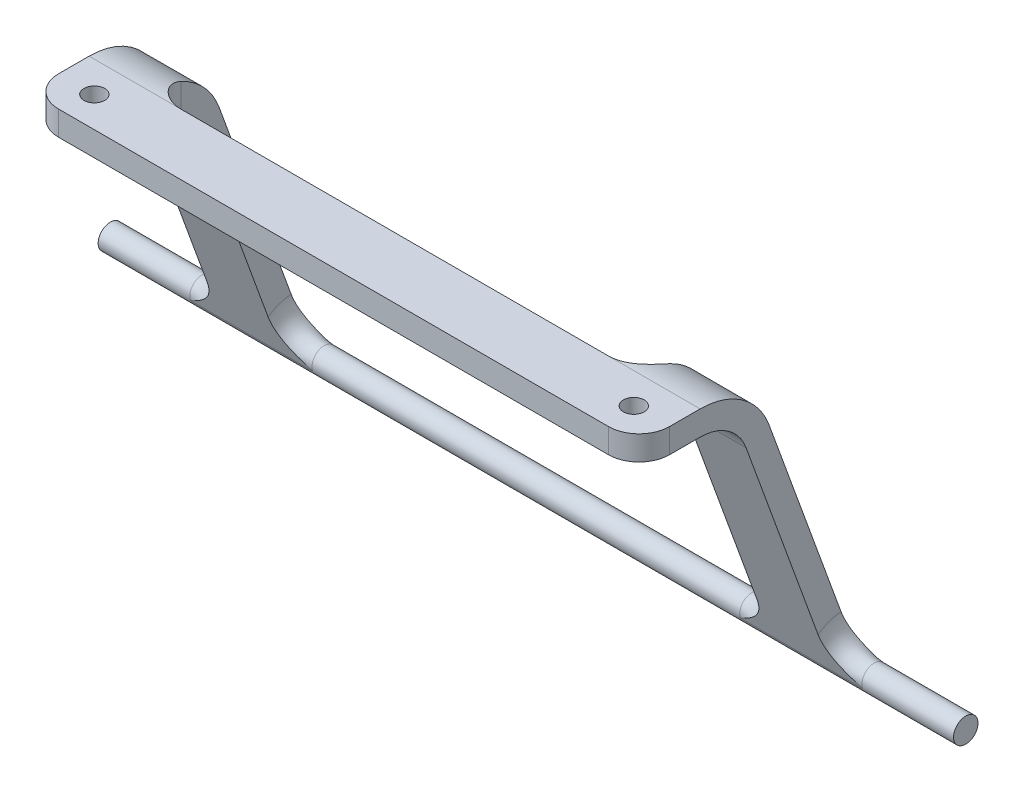
SolidWorks part; units mm, degrees
material "ABS PC"
ref_plane "Front Plane" through (0, 0, 0) normal (0, 0, 1) x (1, 0, 0)
ref_plane "Top Plane" through (0, 0, 0) normal (0, 1, 0) x (1, 0, 0)
ref_plane "Right Plane" through (0, 0, 0) normal (1, 0, 0) x (0, 0, -1)
sketch "Sketch1" plane through (0, 0, 0) normal (0, 1, 0) x (1, 0, 0)
  line L1 (-44.1422, -44.1422) -> (44.1422, -44.1422) construction
  line L2 (-44.1422, -44.1422) -> (-44.1422, 44.1422) construction
  line L3 (-44.1422, 44.1422) -> (44.1422, 44.1422) construction
  line L4 (44.1422, -44.1422) -> (44.1422, 44.1422) construction
  line L5 (-44.1422, -44.1422) -> (44.1422, 44.1422) construction
  line L6 (-44.1422, 44.1422) -> (44.1422, -44.1422) construction
  line L9 (-50, 39.1421) -> (50, 39.1421)
  line L10 (-50, 39.1421) -> (-50, 49.1421)
  line L11 (-50, 49.1421) -> (50, 49.1421)
  line L12 (50, 39.1421) -> (50, 49.1421)
  line L13 (-50, 39.1421) -> (50, 49.1421) construction
  line L14 (-50, 49.1421) -> (50, 39.1421) construction
  circle A0 centre (-44.1422, 44.1422) radius 1.7
  circle A1 centre (44.1422, 44.1422) radius 1.7
  point P0 (0, 0)
  point P8 (0, 44.1422)
  dimension "D2" = 3.4
  dimension "D3" = 3.4
  dimension "D4" = 10
  dimension "D1" = 88.2843
  dimension "D5" = 100
extrude "Boss-Extrude1" add sketch "Sketch1" along normal blind 4
sketch "Sketch3" plane through (50, 0, 0) normal (1, 0, 0) x (0, 0, -1)
  line L0 (49.1421, 4) -> (49.1421, 0) construction
  line L1 (49.1421, -8) -> (49.1421, 0) construction
  line L2 (49.1421, -8) -> (66.0085, -1.8612) construction
  line L3 (56.6597, -5.2638) -> (70.7395, -43.9479)
  line L4 (60.4185, -3.8958) -> (74.4983, -42.5798)
  line L5 (71.2185, -45.2638) -> (74.411, -45.2638) construction
  line L6 (49.1421, 4) -> (49.1421, 0)
  arc A0 (49.1421, 0) -> (56.6597, -5.2638) centre (49.1421, -8) cw
  arc A1 (49.1421, 4) -> (60.4185, -3.8958) centre (49.1421, -8) cw
  arc A2 (70.7395, -43.9479) -> (74.4983, -42.5798) centre (72.6189, -43.2638) ccw
  dimension "D2" = 70
  dimension "D1" = 8
  dimension "D3" = 40
extrude "Boss-Extrude2" add sketch "Sketch3" against normal blind 10
mirror "Mirror8" about plane through (0, 0, 0) normal (1, 0, 0) of "Boss-Extrude2"
sketch "Sketch5" plane through (50, 0, 0) normal (1, 0, 0) x (0, 0, -1)
  line L0 (70.7395, -43.9479) -> (74.4983, -42.5798) construction
  circle A0 centre (72.6189, -43.2638) radius 2
  arc A1 (70.7395, -43.9479) -> (74.4983, -42.5798) centre (72.6189, -43.2638) ccw construction
  arc A2 (70.7395, -43.9479) -> (74.4983, -42.5798) centre (72.6189, -43.2638) ccw construction
  point P4 (72.6189, -43.2638)
  point P7 (72.6189, -43.2638)
extrude "Boss-Extrude3" add sketch "Sketch5" against normal offset from surface 20 and the other way blind 20 up to face at (-50, -10.8255, -55.2054) offset beyond the face yes
fillet "Fillet1" radius 5 4 edges at (-40, -41.3845, -71.9349) (40, -41.3845, -71.9349) (-50, -41.3845, -71.9349) (50, -41.3845, -71.9349)
fillet "Fillet2" radius 5 4 edges at (40, 2, -49.1421) (-40, 2, -49.1421) (-50, 2, -39.1421) (50, 2, -39.1421)
